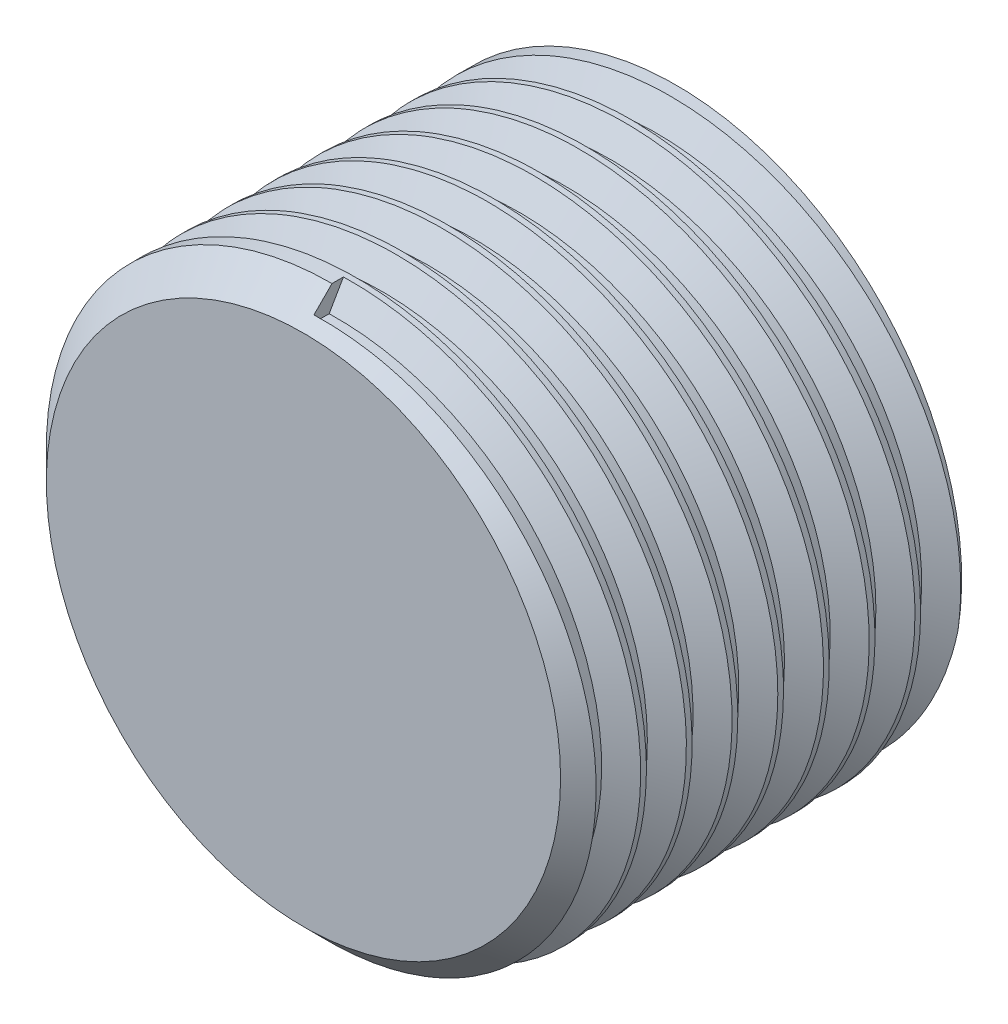
SolidWorks part; units mm, degrees
ref_plane "Спереди" through (0, 0, 0) normal (0, 0, 1) x (1, 0, 0)
ref_plane "Сверху" through (0, 0, 0) normal (0, 1, 0) x (1, 0, 0)
ref_plane "Справа" through (0, 0, 0) normal (1, 0, 0) x (0, 0, -1)
sketch "Эскиз2" plane through (0, 0, 0) normal (0, 0, 1) x (1, 0, 0)
  circle A0 centre (0, 0) radius 5
extrude "Бобышка-Вытянуть1" add sketch "Эскиз2" along normal blind 6.52 contours A0
fillet "Фаска4" radius 0.5 1 edges at (5, 0, 6.52) profile chamfer
thread "Резьба1" pitch 0.8 method cut profile "Профиль резьбы1" start angle 90, offset 0, length 6, pitch 0.8, diameter 10
ref_plane "Плоскость1" through (0, 5, 6.52) normal (-1, 0, 0) x (0, 1, 0)
sketch "Профиль резьбы1" plane through (0, 5, 6.52) normal (-1, 0, 0) x (0, 1, 0)
  line L0 (0, 0) -> (0, 0.8) construction
  line L11 (0, 0) -> (0, 0.7)
  line L12 (0, 0.7) -> (-0.433, 0.45)
  line L13 (-0.433, 0.45) -> (-0.433, 0.25)
  line L15 (-0.433, 0.25) -> (0, 0)
  line L17 (-0.433, 0.35) -> (0, 0.35) construction
  point P2 (0, 0)
  dimension "Pitch" = 0.8
  dimension "Profile_Angle" = 60
  dimension "Profile_Land" = 0.2
  dimension "Profile_Height" = 0.433
sketch "Эскиз25" plane through (0, 0, 0) normal (0, 0, -1) x (-1, 0, 0)
  line L1 (-0.8108, -3.1789) -> (0.7892, -3.1789)
  line L2 (-0.8108, -3.1789) -> (-0.8108, 3.3211)
  line L3 (-0.8108, 3.3211) -> (0.7892, 3.3211)
  line L4 (0.7892, -3.1789) -> (0.7892, 3.3211)
  dimension "D1" = 6.5
  dimension "D2" = 1.6
extrude "Вырез-Вытянуть1" cut sketch "Эскиз25" against normal blind 1 contours L2 L3 L4 L1
